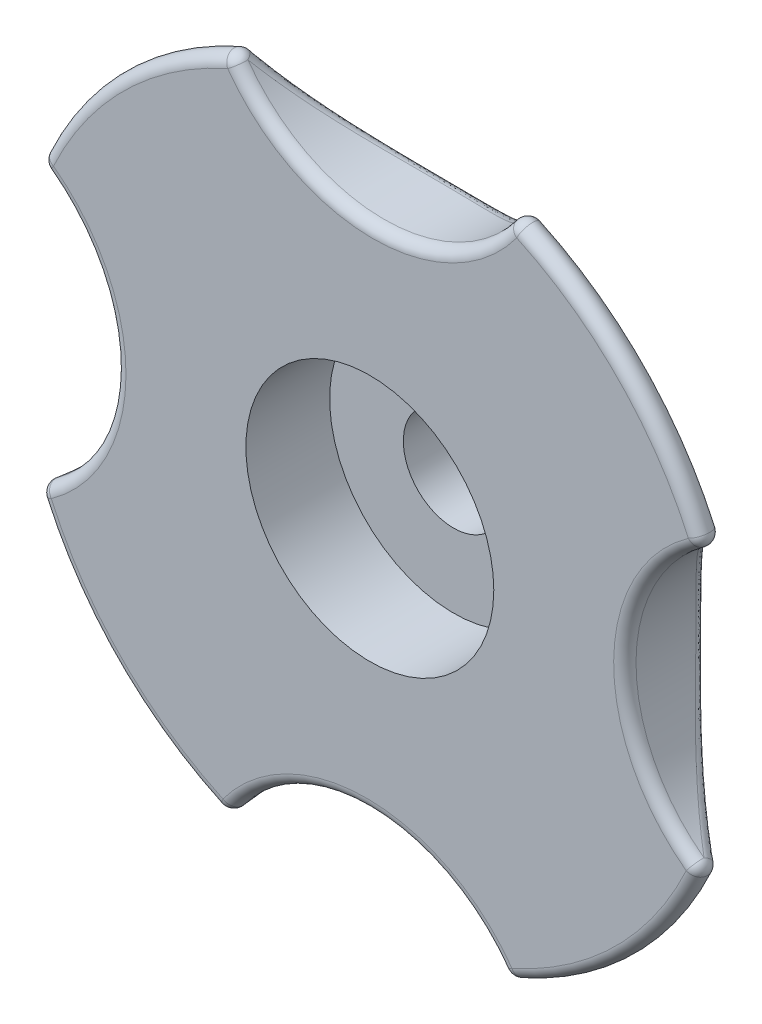
SolidWorks part; units mm, degrees
ref_plane "Спереди" through (0, 0, 0) normal (0, 0, 1) x (1, 0, 0)
ref_plane "Сверху" through (0, 0, 0) normal (0, 1, 0) x (1, 0, 0)
ref_plane "Справа" through (0, 0, 0) normal (1, 0, 0) x (0, 0, -1)
sketch "Эскиз1" plane through (0, 0, 0) normal (0, 1, 0) x (1, 0, 0)
  line L0 (0, 0) -> (-35, 0)
  line L1 (-35, 0) -> (0, 20)
  line L2 (0, 20) -> (0, 0)
  dimension "D1" = 35
  dimension "D2" = 20
revolve "Повернуть1" add sketch "Эскиз1" angle 360 about L2
sketch "Эскиз2" plane through (0, 0, 0) normal (0, 0, 1) x (1, 0, 0)
  circle A0 centre (0, 0) radius 4.5
extrude "Вырез-Вытянуть1" cut sketch "Эскиз2" against normal through all
sketch "Эскиз3" plane through (0, 0, 0) normal (0, 0, 1) x (1, 0, 0)
  circle A0 centre (0, 0) radius 11.1
extrude "Вырез-Вытянуть2" cut sketch "Эскиз3" against normal blind 7.5
sketch "Эскиз4" plane through (0, 0, 0) normal (0, 0, 1) x (1, 0, 0)
  line L0 (0, -38.1173) -> (0, 37.5505) construction
  line L1 (0, 37.5505) -> (37.8339, -0.2834) construction
  line L2 (37.8339, -0.2834) -> (-37.8339, -0.2834) construction
  line L3 (-37.8339, -0.2834) -> (0, 37.5505) construction
  line L4 (-37.8339, -0.2834) -> (0, -38.1173) construction
  line L5 (0, -38.1173) -> (37.8339, -0.2834) construction
  circle A0 centre (37.8339, -0.2834) radius 15
  circle A1 centre (-0.2834, -37.8339) radius 15
  circle A2 centre (-37.8339, 0.2834) radius 15
  circle A3 centre (0.2834, 37.8339) radius 15
  point P15 (0, 0)
  dimension "D1" = 4
extrude "Вырез-Вытянуть3" cut sketch "Эскиз4" against normal through all
fillet "Скругление1" radius 1 12 edges at (0.171, 22.8343, 0) (-1.813, 22.9811, -6.8271) (22.8343, -0.171, 0) (22.9811, 1.813, -6.8271) (-0.171, -22.8343, 0) (1.813, -22.9811, -6.8271) (-22.8343, 0.171, 0) (-22.9811, -1.813, -6.8271) (24.9334, 24.5627, 0) (24.5627, -24.9334, 0) (-24.9334, -24.5627, 0) (-24.5627, 24.9334, 0)
fillet "Скругление2" radius 0.5 1 edges at (4.5, 0, -17.4286)
